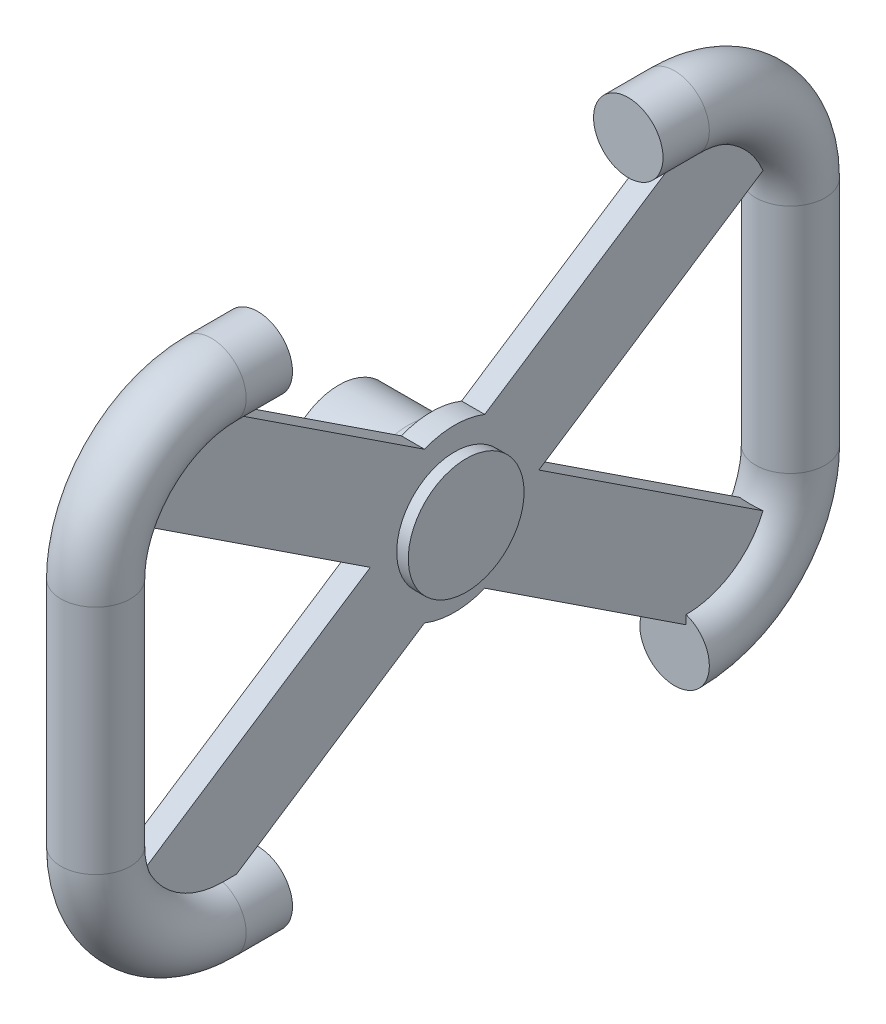
SolidWorks part; units mm, degrees
ref_plane "Front Plane" through (0, 0, 0) normal (0, 0, 1) x (1, 0, 0)
ref_plane "Top Plane" through (0, 0, 0) normal (0, 1, 0) x (1, 0, 0)
ref_plane "Right Plane" through (0, 0, 0) normal (1, 0, 0) x (0, 0, -1)
sketch "Sketch12" plane through (0, 0, 0) normal (1, 0, 0) x (0, 0, -1)
  line L1 (15, 5) -> (15, 15)
  line L2 (10, 20) -> (-10, 20)
  line L3 (-15, 15) -> (-15, 5)
  line L4 (-10, 0) -> (0, 0)
  arc A0 (-10, 20) -> (-15, 15) centre (-10, 15) ccw
  arc A1 (15, 15) -> (10, 20) centre (10, 15) ccw
  arc A2 (-15, 5) -> (-10, 0) centre (-10, 5) ccw
  arc A3 (10, 0) -> (15, 5) centre (10, 5) ccw
  point P4 (0, 0)
  dimension "D1" = 10
  dimension "D3" = 10
  dimension "D4" = 10
  dimension "D5" = 10
  dimension "D6" = 10
  dimension "D2" = 20
sketch "Sketch14" plane through (0, 0, 0) normal (0, 0, 1) x (1, 0, 0)
  circle A0 centre (0, 0) radius 1.5
sweep "Sweep3" add profiles "Sketch14" path "Sketch12"
sketch "Sketch15" plane through (0, 0, 0) normal (0, 0, 1) x (1, 0, 0)
  circle A0 centre (0, 0) radius 1.5
  circle A1 centre (0, 20) radius 1.5
extrude "Cut-Extrude4" cut sketch "Sketch15" against normal mid plane 16
sketch "Sketch16" plane through (0, 0, 0) normal (1, 0, 0) x (0, 0, -1)
  line L0 (1.3013, 13.2491) -> (11.4066, 19.8927)
  line L1 (-13.604, 16.5504) -> (-3.6406, 10)
  line L2 (1.3013, 6.7509) -> (11.4066, 0.1073)
  line L3 (-11.4066, 0.1073) -> (-1.3013, 6.7509)
  line L4 (-11.4066, 19.8927) -> (-1.3013, 13.2491)
  line L5 (-13.604, 3.4496) -> (-3.6406, 10)
  line L6 (3.6406, 10) -> (13.604, 3.4496)
  line L7 (3.6406, 10) -> (13.604, 16.5504)
  arc A0 (1.3013, 13.2491) -> (-1.3013, 13.2491) centre (0, 10) ccw
  circle A1 centre (0, 10) radius 1
  arc A5 (-11.4066, 19.8927) -> (-13.604, 16.5504) centre (0, 10) ccw
  arc A6 (-13.604, 3.4496) -> (-11.4066, 0.1073) centre (0, 10) ccw
  arc A7 (11.4066, 0.1073) -> (13.604, 3.4496) centre (0, 10) ccw
  arc A8 (13.604, 16.5504) -> (11.4066, 19.8927) centre (0, 10) ccw
  arc A9 (-1.3013, 6.7509) -> (1.3013, 6.7509) centre (0, 10) ccw
  dimension "D1" = 7
  dimension "D4" = 2
  dimension "D2" = 15.0989
  dimension "D3" = 4
extrude "Boss-Extrude4" add sketch "Sketch16" along normal mid plane 1
sketch "Sketch17" plane through (0.5, 0, 0) normal (1, 0, 0) x (0, 0, -1)
  circle A0 centre (0, 10) radius 2.5
extrude "Boss-Extrude5" add sketch "Sketch17" along normal blind 0.5
sketch "Sketch18" plane through (-0.5, 0, 0) normal (-1, 0, 0) x (0, 0, 1)
  circle A0 centre (0, 10) radius 2.5
  circle A1 centre (0, 10) radius 1 construction
  circle A2 centre (0, 10) radius 1
extrude "Boss-Extrude6" add sketch "Sketch18" along normal blind 4
fillet "Fillet2" radius 1 1 edges at (-0.5, 10, -2.5)
